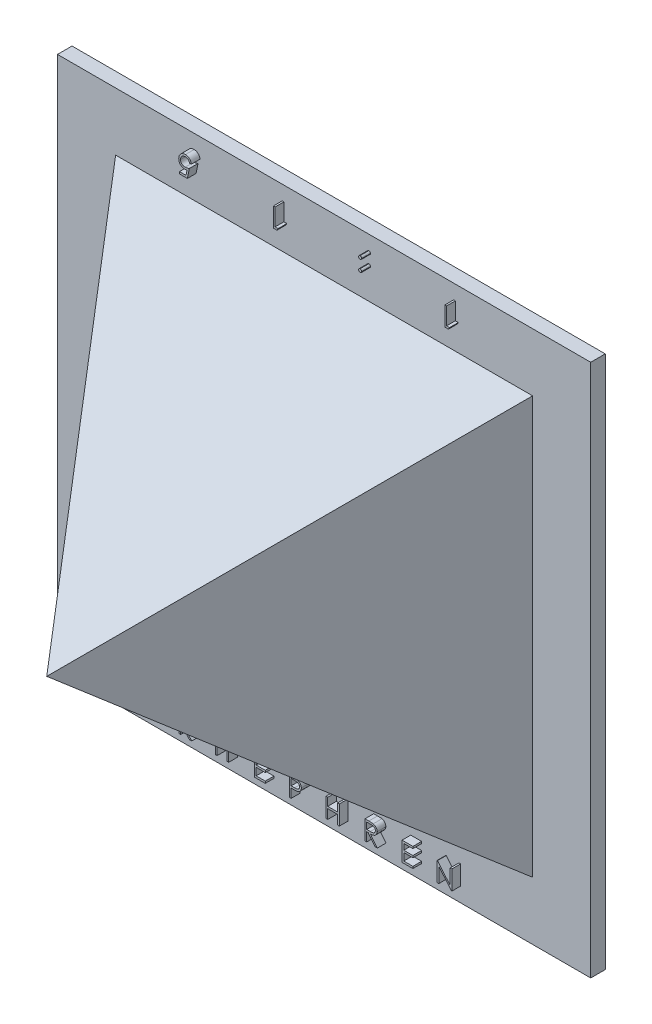
SolidWorks part; units mm, degrees
ref_plane "Plan de face" through (0, 0, 0) normal (0, 0, 1) x (1, 0, 0)
ref_plane "Plan de dessus" through (0, 0, 0) normal (0, 1, 0) x (1, 0, 0)
ref_plane "Plan de droite" through (0, 0, 0) normal (1, 0, 0) x (0, 0, -1)
sketch "Esquisse1" plane through (0, 0, 0) normal (0, 0, 1) x (1, 0, 0)
  line L1 (0, 0) -> (143.44, 0)
  line L2 (0, 0) -> (0, 143.44)
  line L3 (0, 143.44) -> (143.44, 143.44)
  line L4 (143.44, 0) -> (143.44, 143.44)
  dimension "D1" = 143.44
extrude "Boss.-Extru.1" add sketch "Esquisse1" along normal blind 95.9 draft 36.93
sketch "Esquisse3" plane through (0, 0, 0) normal (0, 0, -1) x (-1, 0, 0)
  line L8 (20, -20) -> (20, 163.44)
  line L9 (20, 163.44) -> (-163.44, 163.44)
  line L10 (-163.44, 163.44) -> (-163.44, -20)
  line L11 (-163.44, -20) -> (20, -20)
  line L12 (20, -20) -> (20, 163.44)
  line L13 (20, 163.44) -> (-163.44, 163.44)
  line L14 (-163.44, 163.44) -> (-163.44, -20)
  line L15 (-163.44, -20) -> (20, -20)
  dimension "D1" = 20
extrude "Boss.-Extru.3" add sketch "Esquisse3" along normal blind 5 separate body
sketch "Esquisse2" plane through (0, 0, -5) normal (0, 0, -1) x (-1, 0, 0)
  line L0 (0, 0) -> (-143.44, 0) construction
  line L1 (0, 143.44) -> (0, 0) construction
  circle A0 centre (-71.72, 71.72) radius 23.25
  point P5 (-71.72, 0)
  point P8 (0, 71.72)
  dimension "D1" = 46.5
extrude "Boss.-Extru.2" [suppressed] add sketch "Esquisse2" along normal blind 30
sketch "Esquisse4" plane through (0, 0, 0) normal (0, 0, 1) x (1, 0, 0)
  line L0 (23.9145, -15) -> (119.5255, -15) construction
  line L1 (24.2886, 158.44) -> (119.1514, 158.44) construction
  line L2 (0, 0) -> (143.44, 0) construction
  line L3 (163.44, -20) -> (-20, -20) construction
  line L5 (-20, 163.44) -> (163.44, 163.44) construction
  line L6 (143.44, 143.44) -> (0, 143.44) construction
  text T0 "KHEPHREN" font "Century Gothic" height in points 25
  text T1 "1:15" font "Century Gothic" height in points 25
  point P6 (71.72, 0)
  point P7 (71.72, -15)
  point P12 (71.72, 143.44)
  point P13 (71.72, 158.44)
  dimension "D1" = 5
  dimension "D2" = 5
extrude "Boss.-Extru.4" add sketch "Esquisse4" along normal blind 3
